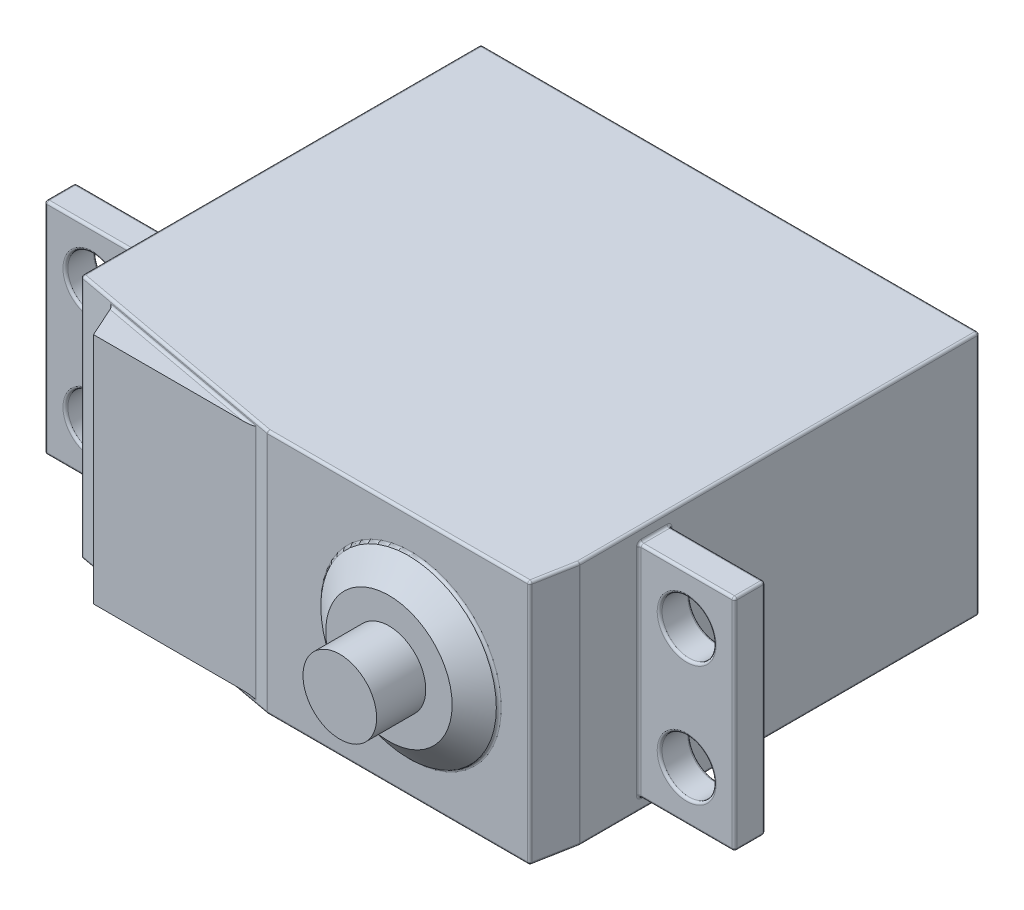
SolidWorks part; units mm, degrees
ref_plane "Front Plane" through (0, 0, 0) normal (0, 0, 1) x (1, 0, 0)
ref_plane "Top Plane" through (0, 0, 0) normal (0, 1, 0) x (1, 0, 0)
ref_plane "Right Plane" through (0, 0, 0) normal (1, 0, 0) x (0, 0, -1)
sketch "Sketch1" plane through (0, 0, 0) normal (0, 1, 0) x (1, 0, 0)
  line L0 (-11.7, 0) -> (9.6632, 0)
  line L1 (9.6632, 0) -> (10.3, 3.4416)
  line L2 (10.3, 3.4416) -> (10.3, 36)
  line L3 (10.3, 36) -> (-30.3, 36)
  line L4 (-30.3, 36) -> (-30.3, 3.4416)
  line L5 (-30.3, 3.4416) -> (-11.7, 0)
  dimension "D1" = 3.5
  dimension "D2" = 22
  dimension "D3" = 10.3
  dimension "D5" = 36
  dimension "D6" = 40.6
extrude "Extrude1" add sketch "Sketch1" along normal mid plane 20
sketch "Sketch2" plane through (0, 0, 0) normal (0, 1, 0) x (1, 0, 0)
  line L0 (10.3, 3.4416) -> (10.3, 36) construction
  line L1 (-38.1, 10.75) -> (18.1, 10.75)
  line L2 (-38.1, 10.75) -> (-38.1, 8.25)
  line L3 (-38.1, 8.25) -> (18.1, 8.25)
  line L4 (18.1, 10.75) -> (18.1, 8.25)
  line L5 (-30.3, 36) -> (-30.3, 3.4416) construction
  line L6 (10.3, 36) -> (-30.3, 36) construction
  dimension "D1" = 7.8
  dimension "D2" = 7.8
  dimension "D3" = 2.5
  dimension "D4" = 27.75
extrude "Extrude2" add sketch "Sketch2" along normal mid plane 17.9
sketch "Sketch3" plane through (0, 0, 0) normal (0, 0, 1) x (1, 0, 0)
  circle A0 centre (0, 0) radius 7.15
  dimension "D1" = 14.3
extrude "Extrude3" add sketch "Sketch3" along normal blind 1.8
sketch "Sketch4" plane through (0, 0, 1.8) normal (0, 0, 1) x (1, 0, 0)
  circle A0 centre (0, 0) radius 3
  dimension "D1" = 6
extrude "Extrude4" add sketch "Sketch4" along normal blind 4
chamfer "Chamfer1" distance 1.6 distance2 2 1 edges at (7.15, 0, 1.8) first distance on face at (7.15, 0, 1.8)
sketch "Sketch5" plane through (0, 0, 0) normal (0, 1, 0) x (1, 0, 0)
  line L0 (-28.3933, 5.3534) -> (-26.0732, 0.2115)
  line L1 (-26.0732, 0.2115) -> (-8.2644, 0.2115)
  line L2 (-8.2644, 0.2115) -> (-28.3933, 5.3534)
extrude "Extrude5" add sketch "Sketch5" along normal mid plane 19
sketch "Sketch6" plane through (0, 0, -8.25) normal (0, 0, 1) x (1, 0, 0)
  line L0 (14.2, -8.95) -> (14.2, -4.9) construction
  line L1 (14.2, 4.9) -> (-34.2, 4.9) construction
  line L2 (14.2, 4.9) -> (14.2, -4.9) construction
  line L3 (14.2, -4.9) -> (-34.2, -4.9) construction
  line L4 (-34.2, 4.9) -> (-34.2, -4.9) construction
  line L5 (10.3, -8.95) -> (18.1, -8.95) construction
  line L6 (14.2, -4.9) -> (18.1, -4.9) construction
  line L7 (18.1, 8.95) -> (18.1, -8.95) construction
  line L8 (18.1, -4.9) -> (-34.2, -8.95) construction
  line L9 (-38.1, -8.95) -> (-30.3, -8.95) construction
  line L10 (-34.2, -8.95) -> (-34.2, -4.9) construction
  line L11 (-34.2, -4.9) -> (-38.1, -4.9) construction
  line L12 (-38.1, 8.95) -> (-38.1, -8.95) construction
  line L13 (-34.2, 4.9) -> (-34.2, 8.95) construction
  line L16 (-38.1, 8.95) -> (-30.3, 8.95) construction
  circle A0 centre (14.2, 4.9) radius 2.2
  circle A1 centre (14.2, -4.9) radius 2.2
  circle A2 centre (-34.2, -4.9) radius 2.2
  circle A3 centre (-34.2, 4.9) radius 2.2
  dimension "D1" = 4.4
  dimension "D2" = 48.4
  dimension "D3" = 9.8
extrude "Extrude6" cut sketch "Sketch6" against normal blind 19
fillet "Fillet2" radius 0.2 55 edges at (10.3, 0, -3.4416) (10.3, 0, -36) (-30.3, 0, -36) (-30.3, 0, -3.4416) (-20.0606, -9.5, -1.547) (-12.8428, 0, -0.2115) (-20.0606, 9.5, -1.547) (-27.2784, 0, -2.8825) (-21, 10, -1.7208) (-30.3, 10, -19.7208) (-10, 10, -36) (10.3, 10, -19.7208) (9.9816, 10, -1.7208) (10.3, -10, -19.7208) (-10, -10, -36) (-30.3, -10, -19.7208) (-21, -10, -1.7208) (9.9816, -10, -1.7208) (-7.15, 0, 0) (-11.7, 0, 0) (-1.0184, 10, 0) (9.6632, 0, 0) (-1.0184, -10, 0) (-38.1, -8.95, -9.5) (-30.3, -8.95, -9.5) (-38.1, 8.95, -9.5) (-30.3, 8.95, -9.5) (-38.1, 0, -10.75) (-34.2, -8.95, -10.75) (-30.3, 0, -10.75) (-34.2, 8.95, -10.75) (-38.1, 0, -8.25) (-34.2, 8.95, -8.25) (-30.3, 0, -8.25) (-34.2, -8.95, -8.25) (10.3, 0, -8.25) (10.3, 0, -10.75) (14.2, 8.95, -10.75) (14.2, 8.95, -8.25) (10.3, 8.95, -9.5) (14.2, -8.95, -10.75) (10.3, -8.95, -9.5) (14.2, -8.95, -8.25) (18.1, 0, -8.25) (18.1, 8.95, -9.5) (18.1, 0, -10.75) (18.1, -8.95, -9.5) (16.4, 4.9, -10.75) (16.4, 4.9, -8.25) (16.4, -4.9, -10.75) (16.4, -4.9, -8.25) (-32, -4.9, -10.75) (-32, -4.9, -8.25) (-32, 4.9, -10.75) (-32, 4.9, -8.25)
